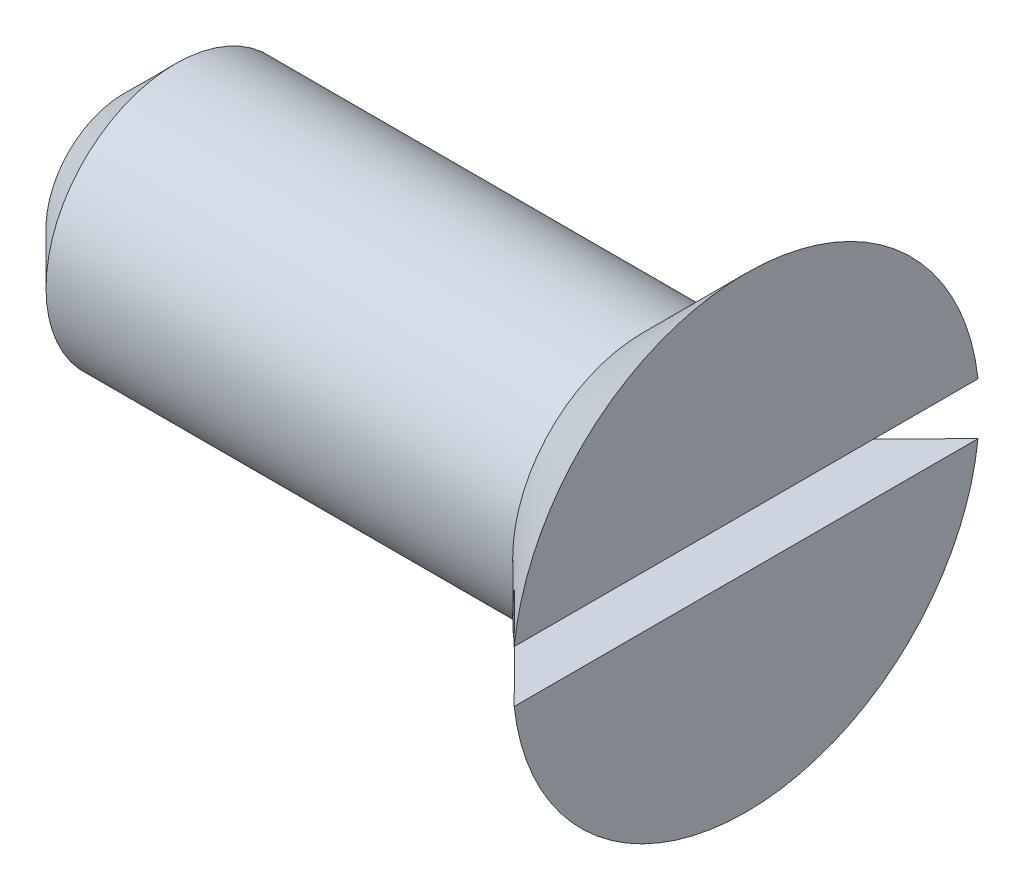
SolidWorks part; units mm, degrees
material "Простая углеродистая сталь"
ref_plane "Спереди" through (0, 0, 0) normal (0, 0, 1) x (1, 0, 0)
ref_plane "Сверху" through (0, 0, 0) normal (0, 1, 0) x (1, 0, 0)
ref_plane "Справа" through (0, 0, 0) normal (1, 0, 0) x (0, 0, -1)
sketch "Эскиз1" plane through (0, 0, 0) normal (0, 1, 0) x (1, 0, 0)
  line L0 (0, 0) -> (12, 0)
  line L5 (0, 2.5) -> (0, 0)
  line L6 (0, 2.5) -> (10, 2.5)
  line L7 (10, 2.5) -> (12, 4.5)
  line L8 (12, 4.5) -> (12, 0)
  dimension "D1" = 2.5
  dimension "D2" = 2
  dimension "D3" = 12
  dimension "D4" = 45
revolve "Повернуть1" add sketch "Эскиз1" angle 360 about L0
chamfer "Фаска1" distance 1 angle 45 1 edges at (0, 0, 2.5)
sketch "Эскиз2" plane through (12, 0, 0) normal (1, 0, 0) x (0, 0, -1)
  line L1 (4.8288, -0.5) -> (-4.8288, -0.5)
  line L2 (4.8288, -0.5) -> (4.8288, 0.5)
  line L3 (4.8288, 0.5) -> (-4.8288, 0.5)
  line L4 (-4.8288, -0.5) -> (-4.8288, 0.5)
  line L5 (4.8288, -0.5) -> (-4.8288, 0.5) construction
  line L6 (4.8288, 0.5) -> (-4.8288, -0.5) construction
  point P0 (0, 0)
  dimension "D1" = 1
extrude "Вырез-Вытянуть1" cut sketch "Эскиз2" against normal blind 1
